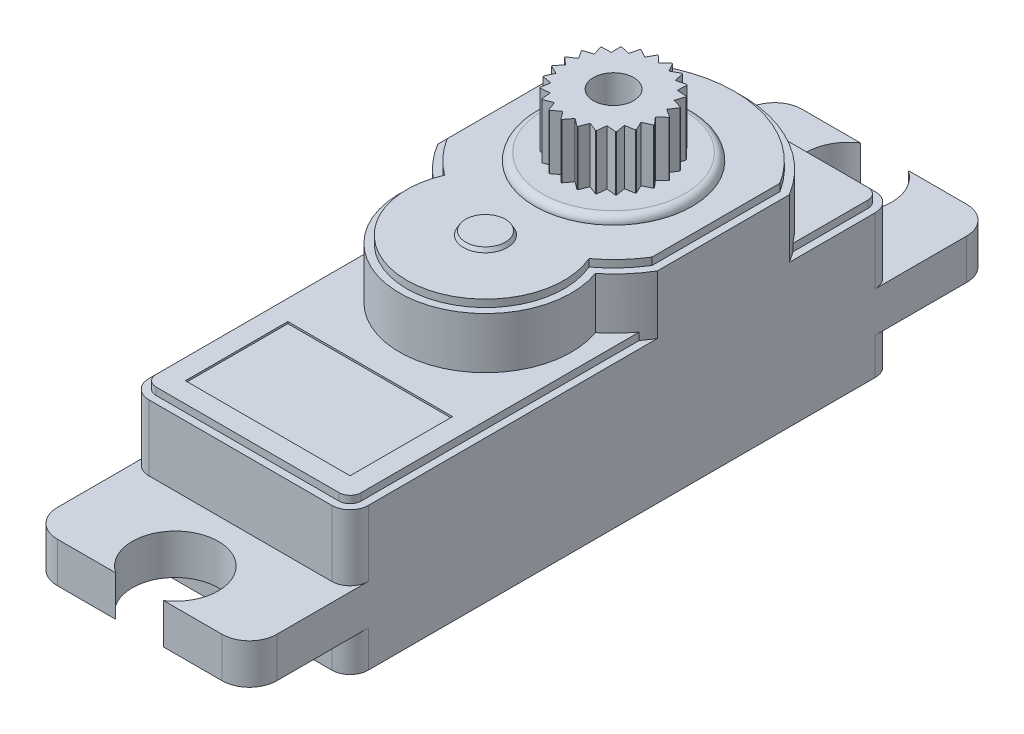
SolidWorks part; units mm, degrees
ref_plane "Front Plane" through (0, 0, 0) normal (0, 0, 1) x (1, 0, 0)
ref_plane "Top Plane" through (0, 0, 0) normal (0, 1, 0) x (1, 0, 0)
ref_plane "Right Plane" through (0, 0, 0) normal (1, 0, 0) x (0, 0, -1)
sketch "Sketch2" plane through (0, 0, 0) normal (0, 1, 0) x (1, 0, 0)
  line L0 (6, -14.85) -> (-6, -14.85)
  line L1 (6, -14.85) -> (6, 14.85)
  line L2 (6, 14.85) -> (-6, 14.85)
  line L3 (-6, -14.85) -> (-6, 14.85)
  line L4 (6, -14.85) -> (-6, 14.85) construction
  line L5 (6, 14.85) -> (-6, -14.85) construction
  point P0 (0, 0)
  dimension "D1" = 12
  dimension "D2" = 29.7
extrude "Boss-Extrude1" add sketch "Sketch2" along normal blind 7.8
sketch "Sketch3" plane through (0, 0, 14.85) normal (0, 0, 1) x (1, 0, 0)
  line L0 (-6, 4.2) -> (6, 4.2)
  line L1 (-6, 4.2) -> (-6, 2)
  line L2 (-6, 2) -> (6, 2)
  line L3 (6, 4.2) -> (6, 2)
  line L4 (-6, 4.2) -> (6, 2) construction
  line L5 (-6, 2) -> (6, 4.2) construction
  line L6 (-6, 0) -> (6, 0) construction
  point P0 (0, 3.1)
  dimension "D1" = 2.2
  dimension "D3" = 2
extrude "Boss-Extrude2" add sketch "Sketch3" along normal blind 5.5
sketch "Sketch4" plane through (0, 4.2, 0) normal (0, 1, 0) x (1, 0, 0)
  circle A0 centre (0, -18.4) radius 2.35
  dimension "D1" = 4.7
  dimension "D3" = 18.4
extrude "Cut-Extrude1" cut sketch "Sketch4" against normal up to next
fillet "Fillet1" radius 1.5 2 edges at (6, 3.1, 20.35) (-6, 3.1, 20.35)
mirror "Mirror1" about plane through (0, 0, 0) normal (0, 0, 1) of "Fillet1", "Cut-Extrude1", "Boss-Extrude2"
fillet "Fillet2" radius 1 8 edges
sketch "Sketch5" plane through (0, 7.8, 0) normal (0, 1, 0) x (1, 0, 0)
  line L0 (5, 14.85) -> (-5, 14.85) construction
  line L3 (-6, 13.85) -> (-6, -13.85) construction
  line L4 (-6, 9.1556) -> (-6, 1.9444)
  line L5 (6, -13.85) -> (6, 13.85) construction
  line L6 (6, 1.9444) -> (6, 9.1556)
  line L7 (-6.7809, 5.55) -> (7.1186, 5.55) construction
  line L8 (-6.7809, -1.45) -> (7.6704, -1.45) construction
  line L9 (0, 13.0627) -> (0, -6.6142) construction
  arc A0 (6, 9.1556) -> (-6, 9.1556) centre (0, 5.55) ccw
  arc A1 (-4.4272, 0.1279) -> (4.4272, 0.1279) centre (0, -1.45) ccw
  arc A2 (-6, 1.9444) -> (-4.4272, 0.1279) centre (0, 5.55) ccw
  arc A3 (4.4272, 0.1279) -> (6, 1.9444) centre (0, 5.55) ccw
  dimension "D1" = 9.3
  dimension "D2" = 7
extrude "Boss-Extrude3" add sketch "Sketch5" along normal blind 3.2
sketch "Sketch6" plane through (0, 11, 0) normal (0, 1, 0) x (1, 0, 0)
  line L0 (-6, 9.1556) -> (-6, 1.9444) construction
  line L1 (-6, 9.1556) -> (-6, 1.9444) construction
  line L2 (6, 1.9444) -> (6, 9.1556) construction
  line L3 (6, 1.9444) -> (6, 9.1556) construction
  line L4 (-5.6, 9.0428) -> (-5.6, 2.0572)
  line L5 (5.6, 2.0572) -> (5.6, 9.0428)
  arc A0 (6, 9.1556) -> (-6, 9.1556) centre (0, 5.55) ccw construction
  arc A1 (6, 9.1556) -> (-6, 9.1556) centre (0, 5.55) ccw construction
  arc A2 (-6, 1.9444) -> (-4.4272, 0.1279) centre (0, 5.55) ccw construction
  arc A3 (-6, 1.9444) -> (-4.4272, 0.1279) centre (0, 5.55) ccw construction
  arc A4 (-4.4272, 0.1279) -> (4.4272, 0.1279) centre (0, -1.45) ccw construction
  arc A5 (-4.4272, 0.1279) -> (4.4272, 0.1279) centre (0, -1.45) ccw construction
  arc A6 (4.4272, 0.1279) -> (6, 1.9444) centre (0, 5.55) ccw construction
  arc A7 (4.4272, 0.1279) -> (6, 1.9444) centre (0, 5.55) ccw
  arc A8 (-5.6, 2.0572) -> (-3.9457, 0.2593) centre (0, 5.55) ccw
  arc A9 (-3.9457, 0.2593) -> (3.9457, 0.2593) centre (0, -1.45) ccw
  arc A10 (3.9457, 0.2593) -> (5.6, 2.0572) centre (0, 5.55) ccw
  arc A11 (5.6, 9.0428) -> (-5.6, 9.0428) centre (0, 5.55) ccw
  dimension "D1" = 0.4
extrude "Boss-Extrude4" add sketch "Sketch6" along normal blind 0.4 contours L5 A11 L4 A8 A9 A10 region at (0, 11, -3.6963)
sketch "Sketch11" plane through (0, 7.8, 0) normal (0, 1, 0) x (1, 0, 0)
  line L6 (-5.6, 13.85) -> (-5.6, -13.85)
  line L7 (-5, -14.45) -> (5, -14.45)
  line L8 (5.6, 13.85) -> (5.6, -13.85)
  line L16 (5, 14.45) -> (-5, 14.45)
  arc A4 (-5.6, -13.85) -> (-5, -14.45) centre (-5, -13.85) ccw
  arc A5 (5, -14.45) -> (5.6, -13.85) centre (5, -13.85) ccw
  arc A10 (5.6, 13.85) -> (5, 14.45) centre (5, 13.85) ccw
  arc A11 (-5, 14.45) -> (-5.6, 13.85) centre (-5, 13.85) ccw
extrude "Boss-Extrude7" add sketch "Sketch11" along normal blind 0.4
sketch "Sketch8" plane through (0, 11.4, 0) normal (0, 1, 0) x (1, 0, 0)
  line L0 (5, 14.85) -> (-5, 14.85) construction
  circle A0 centre (0, -1.45) radius 1.2
  dimension "D1" = 16.3
extrude "Boss-Extrude6" add sketch "Sketch8" along normal blind 0.2 draft 30
sketch "Sketch7" plane through (0, 11.4, 0) normal (0, 1, 0) x (1, 0, 0)
  line L0 (5, 14.85) -> (-5, 14.85) construction
  circle A0 centre (0, 5.55) radius 2.85
  dimension "D1" = 9.3
  dimension "D2" = 5.7
extrude "Boss-Extrude5" add sketch "Sketch7" along normal blind 3.4
sketch "Sketch9" plane through (0, 8.2, 0) normal (0, 1, 0) x (1, 0, 0)
  line L0 (5, -14.85) -> (-5, -14.85) construction
  line L1 (-4.5, -13.35) -> (4.5, -13.35)
  line L2 (-4.5, -13.35) -> (-4.5, -7.75)
  line L3 (-4.5, -7.75) -> (4.5, -7.75)
  line L4 (4.5, -13.35) -> (4.5, -7.75)
  line L5 (-4.5, -13.35) -> (4.5, -7.75) construction
  line L6 (-4.5, -7.75) -> (4.5, -13.35) construction
  line L7 (-6, 1.9444) -> (-6, -13.85) construction
  line L9 (6, -13.85) -> (6, 1.9444) construction
  point P0 (0, -10.55)
  dimension "D1" = 1.5
  dimension "D2" = 5.6
  dimension "D3" = 1.5
  dimension "D4" = 1.5
extrude "Cut-Extrude2" cut sketch "Sketch9" against normal blind 0.1
sketch "Sketch10" plane through (0, 14.8, 0) normal (0, 1, 0) x (1, 0, 0)
  circle A0 centre (0, 5.55) radius 1.1
extrude "Cut-Extrude3" cut sketch "Sketch10" against normal blind 3
sketch "Sketch13" plane through (0, 11.4, 0) normal (0, 1, 0) x (1, 0, 0)
  circle A0 centre (0, 5.55) radius 4.3
extrude "Boss-Extrude8" add sketch "Sketch13" along normal blind 0.4
fillet "Fillet3" radius 0.4 1 edges at (0, 11.8, -1.25)
sketch "Sketch12" plane through (0, 11.8, 0) normal (0, 1, 0) x (1, 0, 0)
  line L0 (0, 8.0102) -> (-0.4662, 8.4764)
  line L1 (0, 8.4) -> (0, 5.55) construction
  line L2 (-0.4662, 8.4764) -> (0.4662, 8.4764)
  line L3 (-1.588, 5.55) -> (1.5356, 5.55) construction
  line L4 (0, 8.0102) -> (0.4662, 8.4764)
  circle A0 centre (0, 5.55) radius 1.1 construction
  circle A2 centre (0, 5.55) radius 2.4602 construction
  dimension "D1" = 45
extrude "Cut-Extrude4" cut sketch "Sketch12" along normal through all
pattern_circular "CirPattern1" count 23 over 360 about axis through (0, 11.8, -5.55) along (0, 1, 0) of "Cut-Extrude4"
